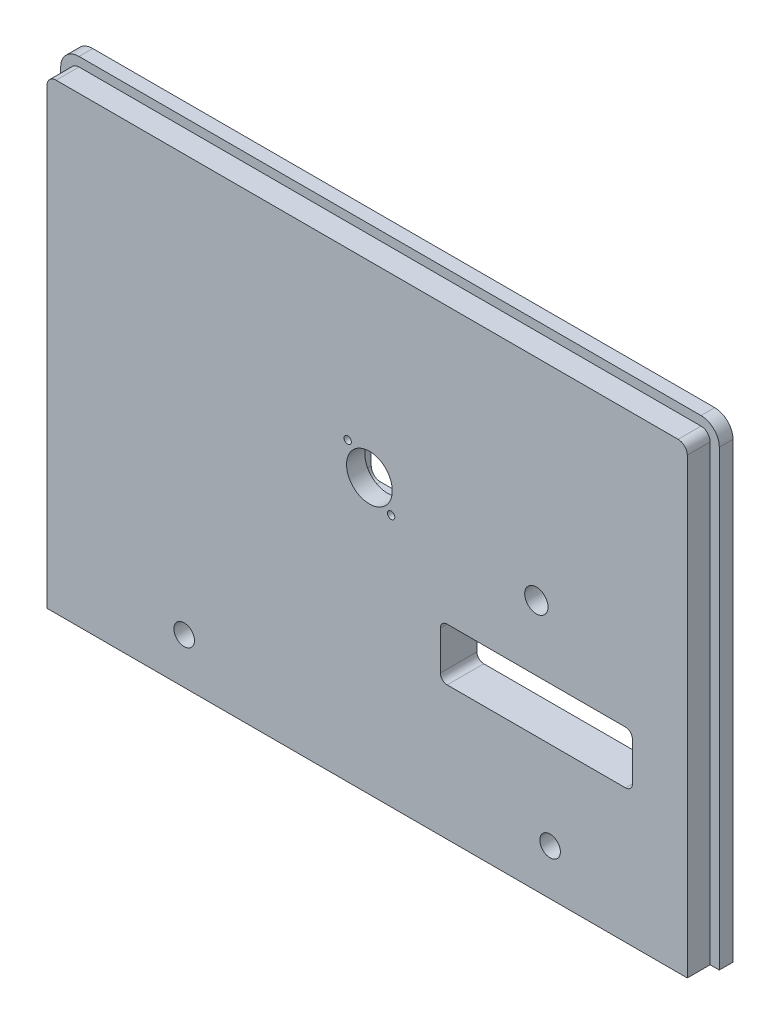
SolidWorks part; units mm, degrees
ref_plane "Front Plane" through (0, 0, 0) normal (0, 0, 1) x (1, 0, 0)
ref_plane "Top Plane" through (0, 0, 0) normal (0, 1, 0) x (1, 0, 0)
ref_plane "Right Plane" through (0, 0, 0) normal (1, 0, 0) x (0, 0, -1)
sketch "Sketch3" plane through (0, 0, 0) normal (0, 0, -1) x (-1, 0, 0)
  line L0 (-70, 20) -> (-70, 0) construction
  line L1 (-70, 0) -> (70, 0)
  line L2 (-70, 0) -> (-70, 99)
  line L3 (-68, 101) -> (68, 101)
  line L4 (70, 0) -> (70, 99)
  line L5 (70, 20) -> (70, 0) construction
  line L6 (-70, 0) -> (70, 0) construction
  line L7 (-54, 86) -> (50, 86) construction
  arc A0 (70, 99) -> (68, 101) centre (68, 99) ccw
  arc A1 (-68, 101) -> (-70, 99) centre (-68, 99) ccw
  point P12 (70, 101)
  dimension "D2" = 2
  dimension "D1" = 15
extrude "Boss-Extrude1" add sketch "Sketch3" along normal blind 8
sketch "Sketch4" plane through (0, 0, -8) normal (0, 0, -1) x (-1, 0, 0)
  line L3 (-72, 0) -> (72, 0)
  line L6 (72, 0) -> (72, 99)
  line L7 (68, 103) -> (-68, 103)
  line L8 (-72, 99) -> (-72, 0)
  line L9 (72, 0) -> (72, 99)
  line L10 (68, 103) -> (-68, 103)
  line L11 (-72, 99) -> (-72, 0)
  arc A4 (72, 99) -> (68, 103) centre (68, 99) ccw
  arc A5 (-68, 103) -> (-72, 99) centre (-68, 99) ccw
  arc A6 (72, 99) -> (68, 103) centre (68, 99) ccw
  arc A7 (-68, 103) -> (-72, 99) centre (-68, 99) ccw
  dimension "D1" = 2
extrude "Boss-Extrude2" add sketch "Sketch4" against normal blind 3
hole_wizard "CSK for M4 Countersunk Flat Head Screw1" positions "3DSketch1" profile "Sketch5" countersink size "M4" standard "ISO" end condition through all
sketch3d "3DSketch1"
  point P0 (40, 10, -8)
  dimension "D1" = 40
  dimension "D2" = 10
sketch "Sketch5" plane through (40, 10, -8) normal (1, 0, 0) x (0, 1, 0)
  line L0 (0, 0) -> (0, 8)
  line L1 (0, 8) -> (2.25, 8)
  line L2 (2.25, 8) -> (2.25, 3.45)
  line L3 (2.25, 3.45) -> (4.7, 1)
  line L4 (4.7, 1) -> (4.7, 0)
  line L6 (4.7, 0) -> (0, 0)
  line L7 (-2.25, 3.45) -> (-4.7, 1) construction
  line L11 (0, -6.35) -> (0, 107.95) construction
  dimension "Thru Hole Dia." = 4.5
  dimension "Thru Hole Depth" = 8
  dimension "C'Sink Dia." = 9.4
  dimension "C'Sink Angle" = 90
  dimension "Head Clearance" = 1
mirror "Mirror1" about plane through (0, 0, 0) normal (1, 0, 0) of "CSK for M4 Countersunk Flat Head Screw1"
sketch "mating_sleeve" plane through (0, 0, -8) normal (0, 0, -1) x (-1, 0, 0)
  line L0 (72, 0) -> (72, 99) construction
  line L1 (-72, 0) -> (72, 0) construction
  point P0 (-0.5, 60)
  dimension "D1" = 72.5
  dimension "D2" = 60
ref_axis "Axis1" through (0.5, 60, -8) along (0, 0, -1)
sketch "Sketch13" plane through (0, 0, -8) normal (0, 0, -1) x (-1, 0, 0)
  line L2 (-8.1, 52.4) -> (7.1, 52.4)
  line L3 (-8.1, 52.4) -> (-8.1, 67.6)
  line L4 (-8.1, 67.6) -> (7.1, 67.6)
  line L5 (7.1, 52.4) -> (7.1, 67.6)
  line L6 (-8.1, 52.4) -> (7.1, 67.6) construction
  line L7 (-8.1, 67.6) -> (7.1, 52.4) construction
  point P0 (-0.5, 60)
  dimension "D1" = 15.2
extrude "Cut-Extrude1" cut sketch "Sketch13" against normal up to surface (4 mm away)
fillet "Fillet1" radius 2 4 edges at (8.1, 52.4, -6) (-7.1, 52.4, -6) (-7.1, 67.6, -6) (8.1, 67.6, -6)
sketch "Sketch14" plane through (0, 0, -8) normal (0, 0, -1) x (-1, 0, 0)
  circle A0 centre (-0.5, 60) radius 5
  dimension "D1" = 10
extrude "Cut-Extrude4" cut sketch "Sketch14" against normal through all
hole_wizard "M2 Tapped Hole1" positions "Sketch16" profile "Sketch15" tap size "M2" standard "ISO" end condition through all
sketch "Sketch16" plane through (0, 0, -4) normal (0, 0, -1) x (-1, 0, 0)
  circle A0 centre (-5.25, 55.25) radius 1.2 construction
  circle A1 centre (4.25, 64.75) radius 1.2 construction
  point P0 (4.25, 64.75)
  point P3 (-5.25, 55.25)
sketch "Sketch15" plane through (-4.25, 64.75, -4) normal (1, 0, 0) x (0, 1, 0)
  line L0 (0, 0) -> (0, 4)
  line L1 (0, 4) -> (0.8, 4)
  line L2 (0.8, 4) -> (0.8, 0)
  line L5 (0.8, 0) -> (0, 0)
  line L11 (0, -6.35) -> (0, 107.95) construction
  dimension "Thread Major Dia." = 1.6
  dimension "Thru Tap Drill Depth" = 4
sketch "DB conn slot" plane through (0, 0, -8) normal (0, 0, -1) x (-1, 0, 0)
  line L0 (-72, 0) -> (72, 0) construction
  line L1 (-72, 99) -> (-72, 0) construction
  line L3 (-56.5, 29.25) -> (-17.5, 29.25)
  line L4 (-58, 30.75) -> (-58, 39.25)
  line L5 (-56.5, 40.75) -> (-17.5, 40.75)
  line L6 (-16, 30.75) -> (-16, 39.25)
  line L7 (-58, 29.25) -> (-16, 40.75) construction
  line L8 (-58, 40.75) -> (-16, 29.25) construction
  arc A0 (-56.5, 29.25) -> (-58, 30.75) centre (-56.5, 30.75) cw
  arc A1 (-17.5, 29.25) -> (-16, 30.75) centre (-17.5, 30.75) ccw
  arc A2 (-17.5, 40.75) -> (-16, 39.25) centre (-17.5, 39.25) cw
  arc A3 (-58, 39.25) -> (-56.5, 40.75) centre (-56.5, 39.25) cw
  point P0 (-37, 35)
  point P5 (-37, 35)
  point P22 (-60.75, 35)
  point P23 (-13.25, 35)
  dimension "D5" = 1.5
  dimension "D1" = 35
  dimension "D2" = 35
  dimension "D3" = 11.5
  dimension "D4" = 42
  dimension "D6" = 23.75
  dimension "D7" = 47.5
ref_axis "DB conn" through (37, 35, -8) along (0, 0, -1)
extrude "Cut-Extrude5" cut sketch "DB conn slot" against normal through all
hole_wizard "M2.5 Tapped Hole1" positions "Sketch19" profile "Sketch18" tap size "M2.5" standard "ISO"
sketch "Sketch19" plane through (0, 0, -8) normal (0, 0, -1) x (-1, 0, 0)
  point P0 (-60.75, 35)
  point P3 (-13.25, 35)
sketch "Sketch18" plane through (60.75, 35, -8) normal (1, 0, 0) x (0, 1, 0)
  line L0 (0, 0) -> (0, 7.8659)
  line L1 (0, 7.8659) -> (1.025, 7.25)
  line L2 (1.025, 7.25) -> (1.025, 0)
  line L5 (1.025, 0) -> (0, 0)
  line L10 (0, 7.8659) -> (-1.025, 7.25) construction
  line L11 (0, -6.35) -> (0, 107.95) construction
  dimension "Tap Drill Dia." = 2.05
  dimension "Tap Drill Depth" = 7.25
  dimension "Drill Angle" = 118
sketch "LED indicator" plane through (0, 0, -8) normal (0, 0, -1) x (-1, 0, 0)
  point P0 (-37, 55)
  dimension "D1" = 20
hole_wizard "CSK for M5 Countersunk Flat Head Screw1" positions "Sketch22" profile "Sketch21" countersink size "M5" standard "ISO" end condition through all
sketch "Sketch22" plane through (0, 0, -8) normal (0, 0, -1) x (-1, 0, 0)
  point P0 (-37, 55)
sketch "Sketch21" plane through (37, 55, -8) normal (1, 0, 0) x (0, 1, 0)
  line L0 (0, 0) -> (0, 8)
  line L1 (0, 8) -> (2.55, 8)
  line L2 (2.55, 8) -> (2.55, 2.65)
  line L3 (2.55, 2.65) -> (5.2, 0)
  line L5 (5.2, 0) -> (0, 0)
  line L6 (-2.55, 2.65) -> (-5.2, 0) construction
  line L11 (0, -6.35) -> (0, 107.95) construction
  dimension "Thru Hole Dia." = 5.1
  dimension "Thru Hole Depth" = 8
  dimension "Near C'Sink Dia." = 10.4
  dimension "Near C'Sink Angle" = 90
ref_axis "LED" through (37, 55, -8) along (0, 0, -1)
